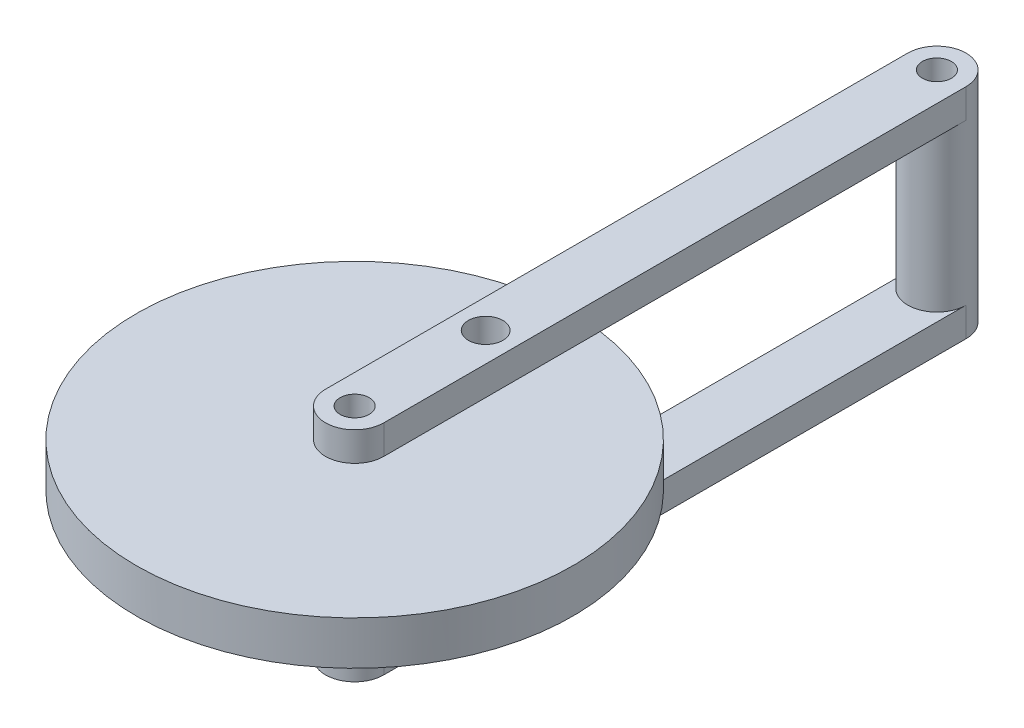
SolidWorks part; units mm, degrees
material "ABS"
ref_plane "Front Plane" through (0, 0, 0) normal (0, 0, 1) x (1, 0, 0)
ref_plane "Top Plane" through (0, 0, 0) normal (0, 1, 0) x (1, 0, 0)
ref_plane "Right Plane" through (0, 0, 0) normal (1, 0, 0) x (0, 0, -1)
sketch "Sketch1" plane through (0, 0, 0) normal (0, 1, 0) x (1, 0, 0)
  line L0 (0, 0) -> (0, -40) construction
  line L1 (2, 0) -> (2, -40)
  line L2 (-2, 0) -> (-2, -40)
  arc A0 (2, 0) -> (-2, 0) centre (0, 0) ccw
  arc A1 (-2, -40) -> (2, -40) centre (0, -40) ccw
  point P3 (0, -20)
  dimension "D2" = 2
  dimension "D1" = 40
extrude "Boss-Extrude1" add sketch "Sketch1" along normal blind 2 contours L1 A1 L2 A0
sketch "Sketch2" plane through (0, 2, 0) normal (0, 1, 0) x (1, 0, 0)
  circle A0 centre (0, 0) radius 2
  dimension "D1" = 4
extrude "Boss-Extrude2" add sketch "Sketch2" along normal blind 12
extrude "Boss-Extrude3" add sketch "Sketch1<3>" along normal blind 2 from offset 13
sketch "Sketch1<3>" plane through (0, 0, 0) normal (0, 1, 0) x (1, 0, 0) same geometry as "Sketch1"
sketch "Sketch7" plane through (0, 13, 0) normal (0, -1, 0) x (1, 0, 0)
  circle A0 centre (0, 40) radius 15
  dimension "D1" = 30
extrude "Boss-Extrude5" add sketch "Sketch7" along normal blind 3
hole_wizard "Ø2.0mm Clearance Dowel Hole1" positions "Sketch4" profile "Sketch5" hole size "Ø2.0" standard "ANSI Metric" end condition through all
sketch "Sketch4" plane through (0, 15, 0) normal (0, 1, 0) x (1, 0, 0)
  point P0 (0, 0)
  point P3 (0, -40)
sketch "Sketch5" plane through (0, 15, 0) normal (1, 0, 0) x (0, 0, 1)
  line L0 (0, 0) -> (0, 15)
  line L1 (0, 15) -> (1, 15)
  line L2 (1, 15) -> (1, 0)
  line L5 (1, 0) -> (0, 0)
  line L11 (0, -6.35) -> (0, 107.95) construction
  dimension "Thru Hole Dia." = 2
  dimension "Thru Hole Depth" = 15
hole_wizard "#4-48 Tapped Hole1" positions "Sketch11" profile "Sketch9" tap size "#4-48" standard "ANSI Inch"
sketch "Sketch11" plane through (0, 15, 0) normal (0, 1, 0) x (1, 0, 0)
  line L0 (0, 0) -> (0, -40) construction
  point P0 (0, -31)
  dimension "D1" = 9
sketch "Sketch9" plane through (0, 15, 31) normal (1, 0, 0) x (0, 0, 1)
  line L0 (0, 0) -> (0, 7.9835)
  line L1 (0, 7.9835) -> (1.1874, 7.27)
  line L2 (1.1874, 7.27) -> (1.1874, 0)
  line L5 (1.1874, 0) -> (0, 0)
  line L10 (0, 7.9835) -> (-1.1875, 7.27) construction
  line L11 (0, -6.35) -> (0, 107.95) construction
  dimension "Tap Drill Dia." = 2.3749
  dimension "Tap Drill Depth" = 7.27
  dimension "Drill Angle" = 118
cosmetic thread "Hole Thread1" parameters "D1"=5, "D2"=2.8448
